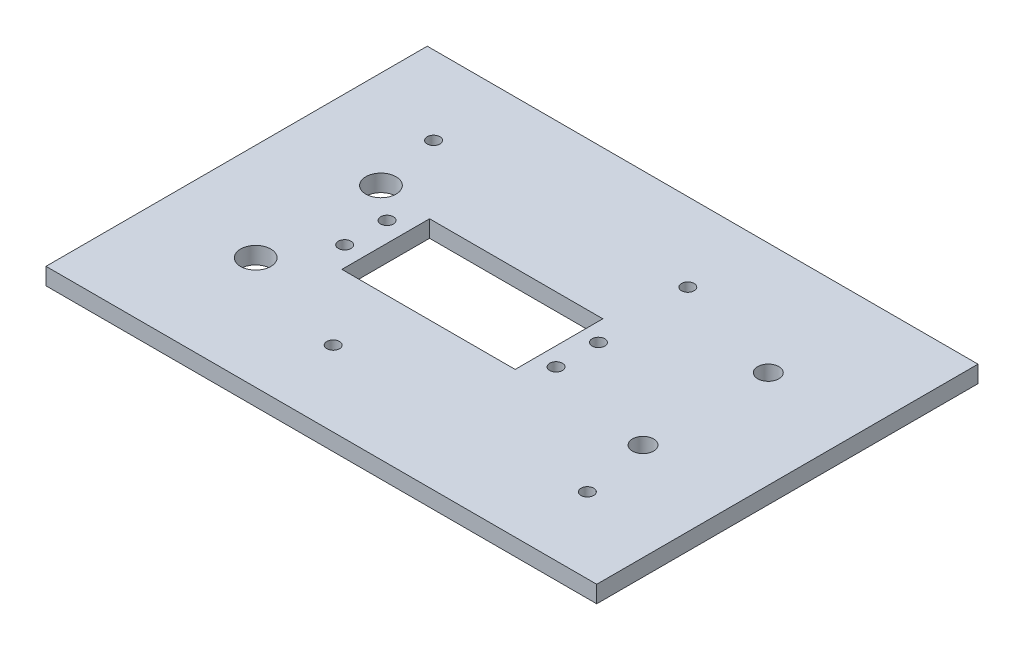
SolidWorks part; units mm, degrees
ref_plane "Front" through (0, 0, 0) normal (0, 0, 1) x (1, 0, 0)
ref_plane "Top" through (0, 0, 0) normal (0, 1, 0) x (1, 0, 0)
ref_plane "Right" through (0, 0, 0) normal (1, 0, 0) x (0, 0, -1)
sketch "Sketch1" plane through (0, 0, 0) normal (0, 1, 0) x (1, 0, 0)
  line L1 (-105, -51.6724) -> (25, -51.6724)
  line L2 (-105, -51.6724) -> (-105, 38.3276)
  line L3 (-105, 38.3276) -> (25, 38.3276)
  line L4 (25, -51.6724) -> (25, 38.3276)
  dimension "D2" = 90
  dimension "D1" = 130
extrude "Boss-Extrude1" add sketch "Sketch1" along normal blind 4
sketch "Sketch2" plane through (0, 4, 0) normal (0, 1, 0) x (1, 0, 0)
  line L1 (25, 38.3276) -> (-105, 38.3276) construction
  line L2 (-105, -51.6724) -> (25, -51.6724) construction
  line L3 (-40, 38.3276) -> (-40, -51.6724) construction
  point P0 (-40, -51.6724)
  point P1 (-40, 38.3276)
sketch "Sketch3" plane through (0, 4, 0) normal (0, 1, 0) x (1, 0, 0)
  line L0 (-92, 30.3276) -> (12, 30.3276) construction
  line L2 (25, 38.3276) -> (-105, 38.3276) construction
  line L3 (-105, -51.6724) -> (25, -51.6724) construction
  line L4 (-40, 38.3276) -> (-40, -51.6724) construction
  circle A0 centre (-92, 30.3276) radius 2.5
  circle A1 centre (12, 30.3276) radius 2.5
  circle A2 centre (12, -43.6724) radius 2.5
  circle A3 centre (-92, -43.6724) radius 2.5
  point P2 (-40, 30.3276)
  dimension "D2" = 5
  dimension "D4" = 5
  dimension "D5" = 5
  dimension "D1" = 5
  dimension "D3" = 104
  dimension "D6" = 8
  dimension "D7" = 8
extrude "Cut-Extrude1" [suppressed] cut sketch "Sketch3" against normal blind 10
sketch "Sketch4" plane through (0, 4, 0) normal (0, 1, 0) x (1, 0, 0)
  line L0 (-49, 14.3276) -> (-31, 14.3276) construction
  line L2 (25, 38.3276) -> (-105, 38.3276) construction
  line L3 (-40, 38.3276) -> (-40, -51.6724) construction
  circle A0 centre (-49, 14.3276) radius 1.15
  circle A1 centre (-31, 14.3276) radius 1.15
  point P4 (-40, 14.3276)
  dimension "D1" = 2.3
  dimension "D2" = 2.3
  dimension "D3" = 18
  dimension "D4" = 24
extrude "Cut-Extrude2" [suppressed] cut sketch "Sketch4" against normal blind 4
sketch "Sketch5" plane through (0, 0, 0) normal (0, -1, 0) x (-1, 0, 0)
  line L1 (-25, 38.3276) -> (105, 38.3276) construction
  line L2 (40, 38.3276) -> (40, -51.6724) construction
  circle A0 centre (40, 18.2946) radius 2
  dimension "D1" = 4
  dimension "D2" = 20.033
extrude "Cut-Extrude3" [suppressed] cut sketch "Sketch5" against normal blind 10
sketch "Sketch7" plane through (0, 4, 0) normal (0, 1, 0) x (1, 0, 0)
  line L0 (-82, 4.3933) -> (-82, -25.1724) construction
  line L1 (2, 11.8276) -> (2, -17.738) construction
  line L2 (25, 38.3276) -> (-105, 38.3276) construction
  line L3 (-40, 38.3276) -> (-40, -51.6724) construction
  line L4 (-105, -51.6724) -> (25, -51.6724) construction
  line L5 (-40, 38.3276) -> (-40, -51.6724) construction
  circle A4 centre (2, 11.8276) radius 3.65
  circle A5 centre (2, -17.738) radius 3.65
  circle A6 centre (-82, 4.3933) radius 3.57
  circle A7 centre (-82, -25.1724) radius 3.57
  point P16 (-40, -6.6724)
  dimension "D2" = 7.14
  dimension "D4" = 7.14
  dimension "D5" = 7.3
  dimension "D8" = 7.3
  dimension "D1" = 84
  dimension "D3" = 26.5
  dimension "D6" = 26.5
  dimension "D7" = 42
  dimension "D9" = 11.0657
  dimension "D10" = 11.0657
extrude "Cut-Extrude5" cut sketch "Sketch7" against normal blind 10
sketch "Sketch15" plane through (0, 4, 0) normal (0, 1, 0) x (1, 0, 0)
  line L0 (-69.45, -7.0305) -> (-28.55, -7.0305) construction
  line L1 (-69.45, 3.3195) -> (-28.55, 3.3195)
  line L2 (-69.45, 3.3195) -> (-69.45, -17.3805)
  line L3 (-69.45, -17.3805) -> (-28.55, -17.3805)
  line L4 (-28.55, 3.3195) -> (-28.55, -17.3805)
  line L6 (-40, 38.3276) -> (-40, -51.6724) construction
  point P6 (-40, -6.6724)
  point P10 (-49, -7.0305)
  dimension "D3" = 0.3581
  dimension "D1" = 40.9
  dimension "D2" = 20.7
  dimension "D10" = 9
extrude "Cut-Extrude10" cut sketch "Sketch15" against normal through all
sketch "Sketch13" plane through (0, 4, 0) normal (0, 1, 0) x (1, 0, 0)
  line L0 (25, 38.3276) -> (-105, 38.3276) construction
  line L1 (-105, 38.3276) -> (-90, 38.3276)
  line L2 (-105, 38.3276) -> (-105, -51.6724)
  line L3 (-105, -51.6724) -> (-90, -51.6724)
  line L4 (-90, 38.3276) -> (-90, -51.6724)
  line L5 (10, 38.3276) -> (25, 38.3276)
  line L6 (10, 38.3276) -> (10, -51.6724)
  line L7 (10, -51.6724) -> (25, -51.6724)
  line L8 (25, 38.3276) -> (25, -51.6724)
  line L9 (25, -51.6724) -> (25, 38.3276) construction
  line L10 (-105, -51.6724) -> (25, -51.6724) construction
  dimension "D1" = 15
  dimension "D2" = 15
extrude "Cut-Extrude9" [suppressed] cut sketch "Sketch13" against normal blind 10
sketch "Sketch10" [suppressed] plane through (0, 4, 0) normal (0, 1, 0) x (1, 0, 0)
  line L0 (10, 38.3276) -> (-90, 38.3276) construction
  line L1 (-90, -51.6724) -> (10, -51.6724) construction
  line L2 (-45.5, 31.3276) -> (-34.5, 31.3276) construction
  line L3 (-45.5, -44.6724) -> (-34.5, -44.6724) construction
  line L4 (-24.3137, -2.9552) -> (-13, 8.3585) construction
  line L5 (-24.3137, -2.9552) -> (-13, -14.2689) construction
  line L6 (-40, 38.3276) -> (-40, -51.6724) construction
  line L7 (2, 11.8276) -> (2, -17.738) construction
  line L8 (-13, -14.2689) -> (-1.6863, -2.9552) construction
  line L9 (-1.6863, -2.9552) -> (-13, 8.3585) construction
  line L10 (-28.55, -17.3805) -> (-28.55, 3.3195) construction
  line L11 (-28.55, -7.0305) -> (-28.55, -17.3805)
  circle A0 centre (-45.5, 31.3276) radius 0.8
  circle A1 centre (-34.5, 31.3276) radius 0.8
  circle A2 centre (-45.5, -44.6724) radius 0.8
  circle A3 centre (-34.5, -44.6724) radius 0.8
  circle A4 centre (-13, -2.9552) radius 8
  circle A5 centre (-24.3137, -2.9552) radius 1
  circle A6 centre (-13, 8.3585) radius 1
  circle A7 centre (-1.6863, -2.9552) radius 1
  circle A8 centre (-13, -14.2689) radius 1
  arc A10 (-28.55, -7.0305) -> (-28.55, -17.3805) centre (-28.55, -12.2055) cw
  point P12 (-40, 31.3276)
  point P27 (2, -2.9552)
  point P36 (-13, -2.9552)
  dimension "D1" = 1.6
  dimension "D5" = 1.6
  dimension "D6" = 1.6
  dimension "D7" = 1.6
  dimension "D8" = 16
  dimension "D11" = 2
  dimension "D12" = 2
  dimension "D13" = 2
  dimension "D14" = 2
  dimension "D2" = 11
  dimension "D3" = 7
  dimension "D4" = 7
  dimension "D9" = 16
  dimension "D10" = 16
  dimension "D18" = 11.3137
  dimension "D19" = 11.3137
  dimension "D15" = 15
extrude "Cut-Extrude7" [suppressed] cut sketch "Sketch10" against normal blind 10
sketch "Sketch6" plane through (0, 0, 0) normal (0, -1, 0) x (1, 0, 0)
  line L6 (-74.1394, 2.0305) -> (-74.1394, 12.0305) construction
  circle A0 centre (-74.1394, 12.0305) radius 1.5
  circle A1 centre (-24.2394, 12.0305) radius 1.5
  circle A2 centre (-74.1394, 2.0305) radius 1.5
  circle A3 centre (-24.2394, 2.0305) radius 1.5
  dimension "D3" = 3
  dimension "D4" = 3
  dimension "D9" = 3
  dimension "D10" = 3
  dimension "D11" = 10
extrude "Cut-Extrude4" cut sketch "Sketch6" against normal blind 4
sketch "Sketch11" plane through (0, 4, 0) normal (0, 1, 0) x (1, 0, 0)
  line L0 (-74.1394, -12.0305) -> (8.7, -12.0305) construction
sketch "Sketch12" plane through (0, 4, 0) normal (0, 1, 0) x (1, 0, 0)
  line L1 (-85, 19.8195) -> (-25, 19.8195) construction
  line L3 (-105, 38.3276) -> (-105, -51.6724) construction
  line L4 (-49, 3.3195) -> (-49, -17.3805) construction
  line L5 (25, -51.6724) -> (25, 38.3276) construction
  line L7 (-28.55, 3.3195) -> (-69.45, 3.3195) construction
  line L8 (-55, -33.8805) -> (5, -33.8805) construction
  line L12 (-69.45, -17.3805) -> (-28.55, -17.3805) construction
  circle A0 centre (-85, 19.8195) radius 1.5
  circle A1 centre (-25, 19.8195) radius 1.5
  circle A2 centre (-55, -33.8805) radius 1.5
  circle A3 centre (5, -33.8805) radius 1.5
  point P16 (-49, 3.3195)
  point P20 (-49, -7.0305)
  point P47 (-49, -17.3805)
  dimension "D3" = 3
  dimension "D4" = 3
  dimension "D1" = 3
  dimension "D2" = 3
  dimension "D6" = 60
  dimension "D8" = 60
  dimension "D7" = 20
  dimension "D9" = 20
  dimension "D5" = 26.85
  dimension "D10" = 26.85
extrude "Cut-Extrude8" cut sketch "Sketch12" against normal through all contours A0 | A2 | A3 | A1 region at (-85, 4, -19.8195) region at (-55, 4, 33.8805) region at (5, 4, 33.8805)
sketch "Sketch14" plane through (0, 4, 0) normal (0, 1, 0) x (1, 0, 0)
  line L0 (2, 11.8276) -> (2, -17.738) construction
  line L1 (-5.8425, 19.5277) -> (9.8425, 19.5277)
  line L2 (-5.8425, 19.5277) -> (-5.8425, -25.4381)
  line L3 (-5.8425, -25.4381) -> (9.8425, -25.4381)
  line L4 (9.8425, 19.5277) -> (9.8425, -25.4381)
  line L6 (23.551, -3.9962) -> (23.6558, -3.94) construction
  circle A0 centre (2, 11.8276) radius 2.5
  circle A1 centre (2, -17.738) radius 2.5
  point P10 (2, -2.9552)
  point P14 (-5.8425, -2.9552)
  point P15 (2, 19.5277)
  dimension "D3" = 5
  dimension "D4" = 5
  dimension "D1" = 15.685
  dimension "D2" = 44.9658
extrude "Boss-Extrude2" add sketch "Sketch14" against normal through all
equation "\"gripper_mainPlate_WheelDist\"=104"
equation "\"D5@Sketch3\"=\"D4@Sketch3\""
equation "\"D1@Sketch3\"=\"D4@Sketch3\""
equation "\"D2@Sketch3\"=\"D4@Sketch3\""
equation "\"D7@Sketch3\"=\"D6@Sketch3\""
equation "\"D2@Sketch4\"=\"D1@Sketch4\""
equation "\"D4@Sketch6\"=\"D3@Sketch6\""
equation "\"D4@Sketch10\"=\"D3@Sketch10\""
equation "\"D5@Sketch10\"=\"D1@Sketch10\""
equation "\"D6@Sketch10\"=\"D1@Sketch10\""
equation "\"D7@Sketch10\"=\"D1@Sketch10\""
equation "\"D4@Sketch7\"=\"D2@Sketch7\""
equation "\"D14@Sketch10\"=\"D11@Sketch10\""
equation "\"D13@Sketch10\"=\"D11@Sketch10\""
equation "\"D12@Sketch10\"=\"D11@Sketch10\""
equation "\"D2@Sketch12\"=\"D1@Sketch12\""
equation "\"D3@Sketch12\"=\"D1@Sketch12\""
equation "\"D4@Sketch12\"=\"D1@Sketch12\""
equation "\"D9@Sketch6\"=\"D3@Sketch6\""
equation "\"D10@Sketch6\"=\"D3@Sketch6\""
equation "\"D8@Sketch12\"=\"D6@Sketch12\""
equation "\"D2@Sketch13\"=\"D1@Sketch13\""
equation "\"D7@Sketch12\"=\"D9@Sketch12\""
equation "\"D19@Sketch10\"=\"D18@Sketch10\""
equation "\"D10@Sketch12\"=\"D5@Sketch12\""
equation "\"D6@Sketch7\"=\"D3@Sketch7\""
equation "\"D7@Sketch7\"=\"D1@Sketch7\"/2"
equation "\"D10@Sketch7\"=\"D9@Sketch7\""
equation "\"D8@Sketch7\"=\"D5@Sketch7\""
equation "\"D4@Sketch14\"=\"D3@Sketch14\""
